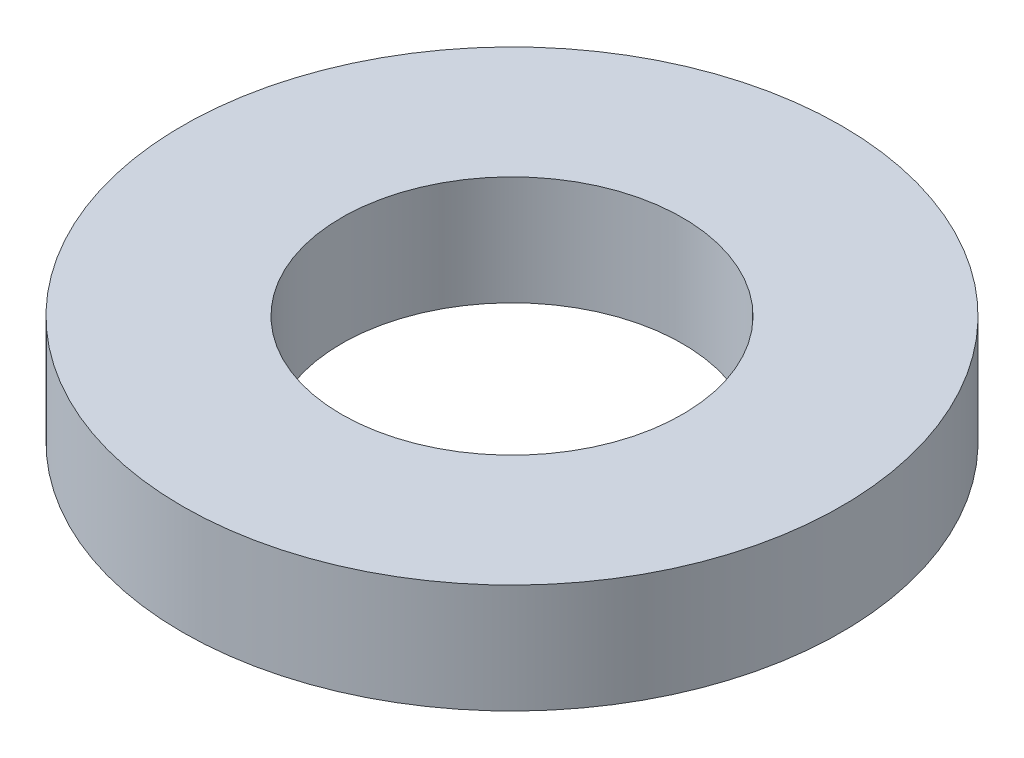
SolidWorks part; units mm, degrees
ref_plane "Front Plane" through (0, 0, 0) normal (0, 0, 1) x (1, 0, 0)
ref_plane "Top Plane" through (0, 0, 0) normal (0, 1, 0) x (1, 0, 0)
ref_plane "Right Plane" through (0, 0, 0) normal (1, 0, 0) x (0, 0, -1)
sketch "Sketch1" plane through (0, 0, 0) normal (0, 1, 0) x (1, 0, 0)
  circle A0 centre (0, 0) radius 72.5
  dimension "FLANGE_OD" = 145
extrude "Boss-Extrude1" add sketch "Sketch1" along normal blind 24
sketch "Sketch2" plane through (0, 0, 0) normal (0, 1, 0) x (1, 0, 0)
  circle A0 centre (0, 0) radius 37.5
  dimension "BORE_D" = 75
extrude "Cut-Extrude1" cut sketch "Sketch2" along normal through all
sketch "Sketch3" plane through (0, 24, 0) normal (0, 1, 0) x (1, 0, 0)
  circle A0 centre (0, 0) radius 22.9721 construction
  circle A1 centre (-22.9721, 0) radius 5.1358
  dimension "BOLT_D" = 10.2717
  dimension "BOLT_PCD" = 45.9442
extrude "Cut-Extrude2" cut sketch "Sketch3" against normal blind 22.198 rebuild error yes
pattern_circular "CirPattern1" count 3 over 360 rebuild error yes
